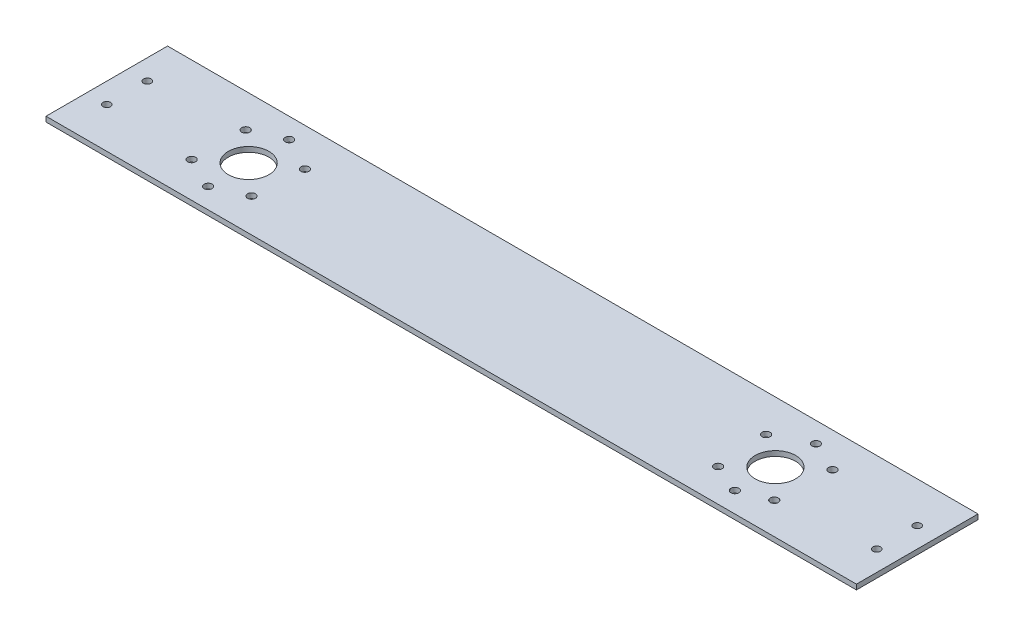
SolidWorks part; units mm, degrees
material "6061 Alloy"
ref_plane "Front Plane" through (0, 0, 0) normal (0, 0, 1) x (1, 0, 0)
ref_plane "Top Plane" through (0, 0, 0) normal (0, 1, 0) x (1, 0, 0)
ref_plane "Right Plane" through (0, 0, 0) normal (1, 0, 0) x (0, 0, -1)
sketch "Sketch1" plane through (0, 0, 0) normal (0, 1, 0) x (1, 0, 0)
  line L1 (254, -38.1) -> (-254, -38.1)
  line L2 (254, -38.1) -> (254, 38.1)
  line L3 (254, 38.1) -> (-254, 38.1)
  line L4 (-254, -38.1) -> (-254, 38.1)
  line L5 (254, -38.1) -> (-254, 38.1) construction
  line L6 (254, 38.1) -> (-254, -38.1) construction
  point P0 (0, 0)
  dimension "D1" = 508
  dimension "D2" = 76.2
extrude "Boss-Extrude1" add sketch "Sketch1" along normal blind 3.175
sketch "Sketch3" plane through (0, 3.175, 0) normal (0, 1, 0) x (1, 0, 0)
  line L1 (-241.3, 38.1) -> (-241.3, 12.7) construction
  line L2 (254, 38.1) -> (-254, 38.1) construction
  line L3 (-241.3, 12.7) -> (-241.3, -12.7) construction
  line L4 (-241.3, -12.7) -> (-241.3, -38.1) construction
  line L5 (-254, -38.1) -> (254, -38.1) construction
  line L6 (-254, 38.1) -> (-254, -38.1) construction
  line L7 (-254, 38.1) -> (254, 38.1) construction
  line L8 (0, 38.1) -> (0, -38.1) construction
  line L9 (241.3, -12.7) -> (241.3, -38.1) construction
  line L10 (241.3, 12.7) -> (241.3, -12.7) construction
  line L11 (241.3, 38.1) -> (241.3, 12.7) construction
  circle A0 centre (-241.3, 12.7) radius 2.3813
  circle A1 centre (-241.3, -12.7) radius 2.3813
  circle A2 centre (241.3, -12.7) radius 2.3813
  circle A3 centre (241.3, 12.7) radius 2.3813
  dimension "D2" = 25.4
  dimension "D3" = 4.7625
  dimension "D1" = 12.7
extrude "Cut-Extrude2" cut sketch "Sketch3" against normal blind 3.175
sketch "Sketch4" plane through (0, 3.175, 0) normal (0, 1, 0) x (1, 0, 0)
  line L0 (-254, 0) -> (-165.1, 0) construction
  line L1 (-254, 38.1) -> (-254, -38.1) construction
  line L2 (0, 38.1) -> (0, -38.1) construction
  line L3 (254, 38.1) -> (-254, 38.1) construction
  line L4 (-254, -38.1) -> (254, -38.1) construction
  line L5 (254, 0) -> (165.1, 0) construction
  circle A0 centre (-165.1, 0) radius 12.7
  circle A1 centre (165.1, 0) radius 12.7
  dimension "D1" = 25.4
  dimension "D2" = 88.9
extrude "Cut-Extrude3" cut sketch "Sketch4" against normal through all both
sketch "Sketch5" plane through (0, 3.175, 0) normal (0, 1, 0) x (1, 0, 0)
  circle A0 centre (-165.1, 0) radius 25.4 construction
  circle A1 centre (165.1, 0) radius 25.4 construction
  circle A2 centre (165.1, 25.4) radius 2.4892
  circle A3 centre (165.1, -25.4) radius 2.4892
  circle A4 centre (182.7023, -18.3117) radius 2.4892
  circle A5 centre (146.7812, -17.595) radius 2.4892
  circle A6 centre (144.4784, 14.8293) radius 2.4892
  circle A7 centre (184.4284, 16.4794) radius 2.4892
  circle A8 centre (-165.1, 25.4) radius 2.4892
  circle A9 centre (-165.1, -25.4) radius 2.4892
  circle A10 centre (-146.2524, -17.0273) radius 2.4892
  circle A11 centre (-144.1426, 14.3509) radius 2.4892
  circle A12 centre (-183.9429, 17.0325) radius 2.4892
  circle A13 centre (-184.8466, -15.976) radius 2.4892
  dimension "D1" = 4.9784
  dimension "D2" = 50.8
  dimension "D3" = 50.8
extrude "Cut-Extrude4" cut sketch "Sketch5" against normal through all both and the other way through all
